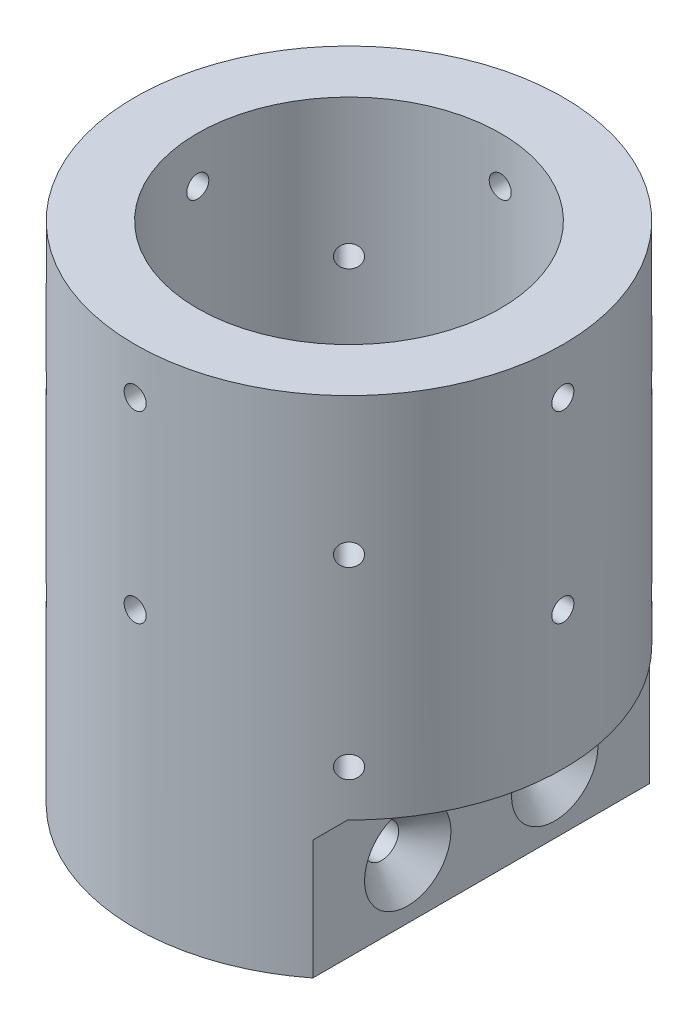
SolidWorks part; units mm, degrees
ref_plane "Спереди" through (0, 0, 0) normal (0, 0, 1) x (1, 0, 0)
ref_plane "Сверху" through (0, 0, 0) normal (0, 1, 0) x (1, 0, 0)
ref_plane "Справа" through (0, 0, 0) normal (1, 0, 0) x (0, 0, -1)
sketch "Эскиз1" plane through (0, 0, 0) normal (0, 1, 0) x (1, 0, 0)
  circle A0 centre (0, 0) radius 23.3
  dimension "D1" = 46.6
extrude "Бобышка-Вытянуть1" add sketch "Эскиз1" along normal blind 5
sketch "Эскиз2" plane through (0, 5, 0) normal (0, 1, 0) x (1, 0, 0)
  circle A0 centre (0, 0) radius 23.3
  circle A1 centre (0, 0) radius 16.5
  circle A2 centre (0, 0) radius 23.3 construction
  dimension "D1" = 33
  dimension "D2" = 0
extrude "Бобышка-Вытянуть2" add sketch "Эскиз2" along normal blind 35
chamfer "Фаска8" distance 2 angle 45 1 edges at (0, 5, 16.5)
sketch "Эскиз3" plane through (0, 0, 0) normal (1, 0, 0) x (0, 0, -1)
  line L0 (-23.3, 20) -> (28.0263, 20) construction
  line L1 (-23.3, 40) -> (-23.3, 0) construction
  line L2 (16.5, 40) -> (-16.5, 40) construction
  circle A1 centre (0, 35) radius 1.2
  dimension "D1" = 2.4
  dimension "D2" = 5
extrude "Вырез-Вытянуть1" cut sketch "Эскиз3" against normal through all
ref_plane "Плоскость1" through (0, 0, 0) normal (0.7071, 0, 0.7071) x (0, -1, 0)
sketch "Эскиз4" plane through (0, 0, 0) normal (0.7071, 0, 0.7071) x (0, -1, 0)
  line L0 (-20, 23.3) -> (-20, -30.0625) construction
  line L1 (0, 23.3) -> (-40, 23.3) construction
  line L3 (0, -23.3) -> (0, 23.3) construction
  circle A1 centre (-5, 0) radius 1.2
  dimension "D1" = 5
  dimension "D2" = 2.4
extrude "Вырез-Вытянуть2" cut sketch "Эскиз4" against normal through all from offset 16.3 offset against normal yes
pattern_circular "Круговой массив1" count 4 over 360 about axis through (0, 5, 0) along (0, -1, 0) of "Вырез-Вытянуть2"
pattern_circular "Круговой массив2" count 4 over 360 about axis through (0, 5, 0) along (0, -1, 0) of "Вырез-Вытянуть1"
pattern_linear "Линейный массив3" count 2 spacing 20 along (0, 1, 0) of "Круговой массив1"
pattern_linear "Линейный массив4" count 2 spacing 20 along (0, -1, 0) of "Круговой массив2"
sketch "Эскиз12" plane through (0, 0, 0) normal (0, -1, 0) x (1, 0, 0)
  line L1 (14.3923, 18.3235) -> (14.3923, -18.3235)
  line L20 (0, 15) -> (-2.7835, 17.7835)
  line L21 (-2.7835, -17.7835) -> (0, -15)
  line L22 (0, -15) -> (0, 15)
  line L23 (0, 15) -> (-2.7835, 17.7835)
  line L24 (-2.7835, -17.7835) -> (0, -15)
  line L25 (0, -15) -> (0, 15)
  circle A6 centre (0, 0) radius 23.3 construction
  arc A7 (14.3923, 18.3235) -> (14.3923, -18.3235) centre (0, 0) ccw
  arc A13 (-2.7835, 17.7835) -> (-2.7835, -17.7835) centre (0, 0) ccw
  arc A14 (-2.7835, 17.7835) -> (-2.7835, -17.7835) centre (0, 0) ccw
  dimension "D1" = 0
extrude "Бобышка-Вытянуть3" add sketch "Эскиз12" along normal blind 15 contours L1 region at (13.7929, 0, 0)
sketch "Эскиз13" plane through (0, -15, 0) normal (0, -1, 0) x (1, 0, 0)
  line L14 (-2.6786, -18.1029) -> (0.3, -15.1243)
  line L15 (0.3, 15.1243) -> (-2.6786, 18.1029)
  line L16 (0.3, -15.1243) -> (0.3, 15.1243)
  line L17 (-2.6786, -18.1029) -> (0.3, -15.1243)
  line L18 (0.3, 15.1243) -> (-2.6786, 18.1029)
  line L19 (0.3, -15.1243) -> (0.3, 15.1243)
  arc A5 (-2.6786, 18.1029) -> (-2.6786, -18.1029) centre (0, 0) ccw
  arc A6 (-2.6786, 18.1029) -> (-2.6786, -18.1029) centre (0, 0) ccw
  dimension "D1" = 0.3
extrude "Вырез-Вытянуть10" cut sketch "Эскиз13" against normal up to surface (15 mm away) up to face at (18.8461, 0, 0)
chamfer "Фаска4" distance 2 angle 45 1 edges at (14.3923, 0, 0)
chamfer "Фаска6" distance 2 angle 45 4 edges at (-1.1893, 0, -16.6136) (-18.3, 0, 0) (0.3, 0, 0) (-1.1893, 0, 16.6136)
chamfer "Фаска7" distance 2 angle 45 4 edges at (-1.1893, -15, -16.6136) (-18.3, -15, 0) (-1.1893, -15, 16.6136) (0.3, -15, 0)
hole_wizard "Зенковка для винта с полупотайной головкой M41" positions "Эскиз14" profile "Эскиз15" countersink size "M4" standard "ISO" end condition through all
sketch "Эскиз14" plane through (14.3923, -676.2045, -24.0267) normal (1, 0, 0) x (0, 0.0202, -0.9998)
  line L0 (-10.4265, 674.5519) -> (-10.6887, 661.5545) construction
  line L4 (-10.5576, 668.0532) -> (-20.4413, 668.0532) construction
  line L5 (-20.4413, 668.0532) -> (-1.8045, 668.0532) construction
  point P0 (-18.5576, 668.0532)
  point P19 (-2.5641, 667.7306)
sketch "Эскиз15" plane through (14.3923, -8.6613, 7.9984) normal (0, 1, 0) x (0, 0, -1)
  line L0 (0, 0) -> (0, 37.6923)
  line L1 (0, 37.6923) -> (1.85, 37.6923)
  line L2 (1.85, 37.6923) -> (1.85, 2.85)
  line L3 (1.85, 2.85) -> (4.7, 0)
  line L4 (4.7, 0) -> (0, 0)
  line L5 (-1.85, 2.85) -> (-4.7, 0) construction
  line L6 (0, -6.35) -> (0, 107.95) construction
  dimension "Диаметр сквозного отверстия" = 3.7
  dimension "Глубина сквозного отверстия" = 37.6923
  dimension "Диаметр передней зенковки" = 9.4
  dimension "Угол передней зенковки" = 90
